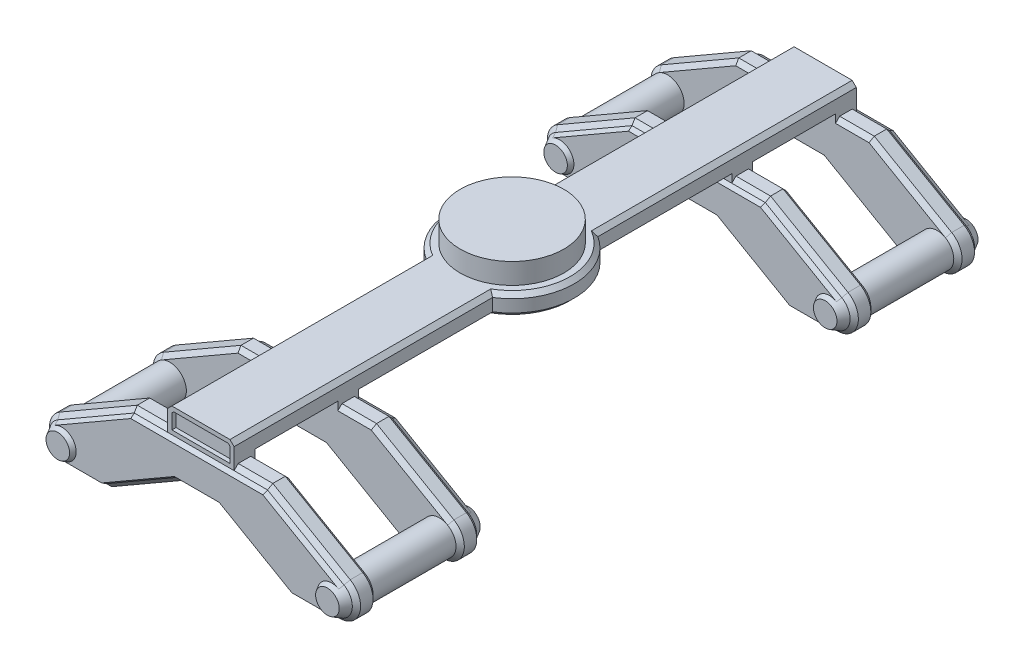
SolidWorks part; units mm, degrees
ref_plane "Front Plane" through (0, 0, 0) normal (0, 0, 1) x (1, 0, 0)
ref_plane "Top Plane" through (0, 0, 0) normal (0, 1, 0) x (1, 0, 0)
ref_plane "Right Plane" through (0, 0, 0) normal (1, 0, 0) x (0, 0, -1)
sketch "Master Sketch" plane through (0, 0, 0) normal (0, 0, 1) x (1, 0, 0)
  line L0 (0, 0) -> (0, -62.5) construction
  line L1 (0, -62.5) -> (-300, -62.5) construction
  line L2 (0, 0) -> (-300, 0)
  line L3 (-300, 0) -> (-300, -62.5) construction
  line L4 (-300, 0) -> (-300, 20)
  line L5 (-300, 20) -> (0, 20)
  line L6 (0, 20) -> (0, 0)
  line L7 (-40, 20) -> (-40, 90)
  line L8 (-40, 90) -> (-260, 90)
  line L9 (-260, 90) -> (-260, 20)
  line L10 (-260, 90) -> (-260, 105)
  line L11 (-260, 105) -> (-80, 105)
  line L12 (-80, 105) -> (-40, 90) construction
  line L13 (-295, 20) -> (-295, 55)
  line L14 (-295, 55) -> (-260, 75)
  line L15 (-265, -37.5) -> (-300, -37.5) construction
  line L16 (-265, -37.5) -> (-200, -37.5) construction
  line L17 (-150, 0) -> (-150, -62.5) construction
  line L18 (-200, -37.5) -> (-150, -37.5) construction
  line L19 (-265, -42.5) -> (-255, -42.5)
  line L20 (-255, -42.5) -> (-237.4963, -32.3942)
  line L21 (-237.4963, -32.3942) -> (-227.5037, -32.3942)
  line L22 (-227.5037, -32.3942) -> (-210, -42.5)
  line L23 (-210, -42.5) -> (-200, -42.5)
  line L24 (-232.5, -32.3942) -> (-232.5, -37.5) construction
  line L25 (-248.836, -22.3942) -> (-267.5, -33.1699)
  line L26 (-248.836, -22.3942) -> (-216.164, -22.3942)
  line L27 (-216.164, -22.3942) -> (-197.5, -33.1699)
  line L28 (-232.5, -32.3942) -> (-232.5, -22.3942) construction
  line L29 (-65, 90) -> (-65, 78.8255) construction
  line L30 (-242.5, -22.3942) -> (-222.5, -22.3942)
  line L31 (-242.5, -22.3942) -> (-242.5, -17.3942)
  line L32 (-242.5, -17.3942) -> (-222.5, -17.3942)
  line L33 (-222.5, -22.3942) -> (-222.5, -17.3942)
  line L35 (-247.5, -12.3942) -> (-217.5, -12.3942)
  line L36 (-247.5, -12.3942) -> (-247.5, -17.3942)
  line L37 (-247.5, -17.3942) -> (-217.5, -17.3942)
  line L38 (-217.5, -12.3942) -> (-217.5, -17.3942)
  circle A0 centre (-265, -37.5) radius 25
  circle A1 centre (-200, -37.5) radius 25
  circle A2 centre (-265, -37.5) radius 5
  circle A3 centre (-200, -37.5) radius 5
  arc A4 (-80, 105) -> (-65, 90) centre (-80, 90) cw
  point P50 (0, 0)
  point P51 (0, 0)
  point P52 (0, 0)
  point P53 (0, 0)
  dimension "D12" = 50
  dimension "D15" = 10
  dimension "D16" = 10
  dimension "D1" = 62.5
  dimension "D2" = 300
  dimension "D3" = 20
  dimension "D4" = 40
  dimension "D5" = 40
  dimension "D6" = 70
  dimension "D7" = 180
  dimension "D8" = 15
  dimension "D9" = 5
  dimension "D10" = 35
  dimension "D11" = 15
  dimension "D13" = 35
  dimension "D14" = 65
  dimension "D17" = 10
  dimension "D18" = 150
  dimension "D19" = 150
  dimension "D20" = 10
  dimension "D21" = 10
  dimension "D22" = 10
  dimension "D23" = 5
  dimension "D24" = 11.1745
  dimension "D25" = 5
  dimension "D26" = 5
  dimension "D27" = 5
sketch "Sketch95" plane through (0, 0, 0) normal (0, 0, 1) x (1, 0, 0)
  line L0 (-248.836, -22.3942) -> (-216.164, -22.3942) construction
  line L1 (-216.164, -22.3942) -> (-197.5, -33.1699) construction
  line L2 (-210, -42.5) -> (-200, -42.5) construction
  line L3 (-227.5037, -32.3942) -> (-210, -42.5) construction
  line L4 (-237.4963, -32.3942) -> (-227.5037, -32.3942) construction
  line L5 (-255, -42.5) -> (-237.4963, -32.3942) construction
  line L6 (-265, -42.5) -> (-255, -42.5) construction
  line L7 (-248.836, -22.3942) -> (-267.5, -33.1699) construction
  line L8 (-248.836, -22.3942) -> (-216.164, -22.3942)
  line L9 (-216.164, -22.3942) -> (-197.5, -33.1699)
  line L10 (-210, -42.5) -> (-200, -42.5)
  line L11 (-227.5037, -32.3942) -> (-210, -42.5)
  line L12 (-237.4963, -32.3942) -> (-227.5037, -32.3942)
  line L13 (-255, -42.5) -> (-237.4963, -32.3942)
  line L14 (-265, -42.5) -> (-255, -42.5)
  line L15 (-248.836, -22.3942) -> (-267.5, -33.1699)
  line L16 (-222.5, -22.3942) -> (-222.5, -17.3942) construction
  line L17 (-242.5, -22.3942) -> (-242.5, -17.3942) construction
  line L18 (-222.5, -22.3942) -> (-222.5, -17.3942)
  line L19 (-242.5, -22.3942) -> (-242.5, -17.3942)
  line L20 (-242.5, -17.3942) -> (-222.5, -17.3942)
  circle A0 centre (-200, -37.5) radius 5 construction
  circle A1 centre (-265, -37.5) radius 5 construction
  circle A2 centre (-200, -37.5) radius 5
  circle A3 centre (-265, -37.5) radius 5
extrude "Boss-Extrude15" add sketch "Sketch95" along normal blind 5 contours A3 | A3 L14 L13 L12 L11 L10 A2 L9 L8 L15 | A2 | L20 L19 L8 L18 region at (-232.5, -31.1523, 0) region at (-232.5, -19.8942, 0) region at (-265, -37.5, 0) region at (-200, -37.5, 0)
sketch "Sketch107" plane through (0, 0, 5) normal (0, 0, 1) x (1, 0, 0)
  line L0 (-222.5, -22.3942) -> (-216.164, -22.3942) construction
  line L1 (-242.5, -17.3942) -> (-240.5, -17.3942)
  line L2 (-242.5, -17.3942) -> (-242.5, -22.3942)
  line L3 (-242.5, -22.3942) -> (-240.5, -22.3942)
  line L4 (-240.5, -17.3942) -> (-240.5, -22.3942)
  line L5 (-222.5, -17.3942) -> (-224.5, -17.3942)
  line L6 (-222.5, -17.3942) -> (-222.5, -22.3942)
  line L7 (-222.5, -22.3942) -> (-224.5, -22.3942)
  line L8 (-224.5, -17.3942) -> (-224.5, -22.3942)
  line L9 (-248.836, -22.3942) -> (-242.5, -22.3942) construction
  dimension "D1" = 2
extrude "Cut-Extrude13" cut sketch "Sketch107" against normal through all
sketch "Sketch96" plane through (0, 0, 5) normal (0, 0, 1) x (1, 0, 0)
  line L7 (-240.5, -17.3942) -> (-224.5, -17.3942)
  line L8 (-240.5, -17.3942) -> (-240.5, -22.3942)
  line L9 (-240.5, -22.3942) -> (-224.5, -22.3942)
  line L10 (-224.5, -17.3942) -> (-224.5, -22.3942)
extrude "Boss-Extrude16" add sketch "Sketch96" along normal blind 10
sketch "Sketch97" plane through (0, 0, 0) normal (0, 0, -1) x (-1, 0, 0)
  line L55 (224.5, -23.3942) -> (240.5, -23.3942)
  line L64 (248.5681, -23.3942) -> (240.5, -23.3942)
  line L65 (267, -34.0359) -> (248.5681, -23.3942)
  line L66 (255.2679, -41.5) -> (265, -41.5)
  line L67 (237.7642, -31.3942) -> (255.2679, -41.5)
  line L68 (227.2358, -31.3942) -> (237.7642, -31.3942)
  line L69 (209.7321, -41.5) -> (227.2358, -31.3942)
  line L70 (200, -41.5) -> (209.7321, -41.5)
  line L71 (216.4319, -23.3942) -> (198, -34.0359)
  line L72 (224.5, -23.3942) -> (216.4319, -23.3942)
  line L73 (248.5681, -23.3942) -> (240.5, -23.3942)
  line L74 (267, -34.0359) -> (248.5681, -23.3942)
  line L75 (255.2679, -41.5) -> (265, -41.5)
  line L76 (237.7642, -31.3942) -> (255.2679, -41.5)
  line L77 (227.2358, -31.3942) -> (237.7642, -31.3942)
  line L78 (209.7321, -41.5) -> (227.2358, -31.3942)
  line L79 (200, -41.5) -> (209.7321, -41.5)
  line L80 (216.4319, -23.3942) -> (198, -34.0359)
  line L81 (224.5, -23.3942) -> (216.4319, -23.3942)
  arc A14 (265, -41.5) -> (267, -34.0359) centre (265, -37.5) ccw
  arc A15 (198, -34.0359) -> (200, -41.5) centre (200, -37.5) ccw
  arc A16 (265, -41.5) -> (267, -34.0359) centre (265, -37.5) ccw
  arc A17 (198, -34.0359) -> (200, -41.5) centre (200, -37.5) ccw
  dimension "D1" = 1
extrude "Boss-Extrude17" add sketch "Sketch97" along normal blind 1 draft 30
sketch "Sketch98" plane through (0, 0, -1) normal (0, 0, -1) x (-1, 0, 0)
  circle A0 centre (200, -37.5) radius 3.4226
  circle A1 centre (265, -37.5) radius 3.4226
extrude "Boss-Extrude18" add sketch "Sketch98" along normal blind 1 draft 30
sketch "Sketch100" plane through (0, 0, 5) normal (0, 0, 1) x (1, 0, 0)
  circle A0 centre (-265, -37.5) radius 4
  circle A1 centre (-200, -37.5) radius 4
  dimension "D1" = 8
  dimension "D2" = 8
extrude "Boss-Extrude19" add sketch "Sketch100" along normal blind 10
chamfer "Chamfer9" distance 1 angle 45 22 edges at (-220.332, -22.3942, 5) (-206.832, -27.782, 5) (-195.1704, -38.7941, 5) (-205, -42.5, 5) (-218.7519, -37.4471, 5) (-232.5, -32.3942, 5) (-246.2481, -37.4471, 5) (-260, -42.5, 5) (-269.8296, -38.7941, 5) (-244.668, -22.3942, 5) (-258.168, -27.782, 5) (-206.832, -27.782, 0) (-195.1704, -38.7941, 0) (-205, -42.5, 0) (-218.7519, -37.4471, 0) (-232.5, -32.3942, 0) (-246.2481, -37.4471, 0) (-220.332, -22.3942, 0) (-260, -42.5, 0) (-269.8296, -38.7941, 0) (-244.668, -22.3942, 0) (-258.168, -27.782, 0)
chamfer "Chamfer10" distance 1 angle 45 4 edges at (-240.5, -17.3942, 7.5) (-224.5, -17.3942, 7.5) (-240.5, -22.3942, 10) (-224.5, -22.3942, 10)
mirror "Mirror5" about plane through (0, 0, 15) normal (0, 0, 1) of bodies 138
sketch "Sketch103" plane through (0, 0, 30) normal (0, 0, 1) x (1, 0, 0)
  line L11 (-239.5, -17.3942) -> (-240.5, -18.3942)
  line L12 (-240.5, -18.3942) -> (-240.5, -22.3942)
  line L13 (-240.5, -23.3942) -> (-240.5, -18.3942) construction
  line L14 (-240.5, -22.3942) -> (-224.5, -22.3942)
  line L15 (-224.5, -18.3942) -> (-224.5, -23.3942) construction
  line L16 (-224.5, -22.3942) -> (-224.5, -18.3942)
  line L17 (-224.5, -18.3942) -> (-225.5, -17.3942)
  line L18 (-225.5, -17.3942) -> (-239.5, -17.3942)
  point P5 (0, 0)
extrude "Boss-Extrude22" add sketch "Sketch103" along normal blind 45
chamfer "Chamfer11" distance 1 angle 45 2 edges at (-224.5, -22.3942, 52.5) (-240.5, -22.3942, 52.5)
sketch "Sketch104" plane through (0, 0, 0) normal (0, 0, -1) x (-1, 0, 0)
  line L10 (225.5, -18.8084) -> (225.5, -22.3942)
  line L11 (225.5, -18.8084) -> (225.5, -22.3942)
  line L12 (239.0858, -18.3942) -> (225.9142, -18.3942)
  line L13 (239.5, -22.3942) -> (239.5, -18.8084)
  line L14 (239.5, -22.3942) -> (239.5, -18.8084)
  line L15 (225.5, -22.3942) -> (239.5, -22.3942)
  line L18 (239.0858, -18.3942) -> (225.9142, -18.3942)
  line L21 (225.5, -22.3942) -> (239.5, -22.3942)
  line L24 (239.5, -18.8084) -> (239.0858, -18.3942)
  line L25 (239.5, -18.8084) -> (239.0858, -18.3942)
  line L26 (225.9142, -18.3942) -> (225.5, -18.8084)
  line L27 (225.9142, -18.3942) -> (225.5, -18.8084)
  dimension "D1" = 1
extrude "Cut-Extrude12" cut sketch "Sketch104" against normal blind 1
mirror "Mirror6" about plane through (0, 0, 75) normal (0, 0, 1) of bodies 144
sketch "Sketch105" plane through (0, -17.3942, 0) normal (0, 1, 0) x (1, 0, 0)
  line L0 (-239.5, -75) -> (-225.5, -75) construction
  line L3 (-247.5, 0) -> (-217.5, 0) construction
  line L4 (-247.5, 0) -> (-217.5, 0)
  line L5 (-217.5, 0) -> (-217.5, -75) construction
  line L6 (-225.5, -150) -> (-225.5, 0) construction
  line L7 (-239.5, 0) -> (-239.5, -150) construction
  circle A0 centre (-232.5, -75) radius 15
  point P2 (-225.5, -75)
  point P5 (-239.5, -75)
extrude "Boss-Extrude23" add sketch "Sketch105" against normal up to surface (5 mm away) contours A0 | A0 | A0 region at (-232.5, -17.3942, 75) up to face at (-232.5, -22.3942, 75)
chamfer "Chamfer12" distance 1 angle 45 4 edges at (-247.5, -22.3942, 75) (-247.5, -17.3942, 75) (-217.5, -22.3942, 75) (-217.5, -17.3942, 75)
sketch "Sketch106" plane through (0, -17.3942, 0) normal (0, 1, 0) x (1, 0, 0)
  line L0 (-246.5, -75) -> (-218.5, -75) construction
  circle A2 centre (-232.5, -75) radius 12.5
  arc A3 (-225.5, -87.1244) -> (-225.5, -62.8756) centre (-232.5, -75) ccw construction
  arc A4 (-239.5, -62.8756) -> (-239.5, -87.1244) centre (-232.5, -75) ccw construction
  point P2 (-218.5, -75)
  point P6 (-246.5, -75)
  dimension "D1" = 25
extrude "Boss-Extrude24" add sketch "Sketch106" along normal up to vertex up to point (-247.5, -12.3942, 0)
